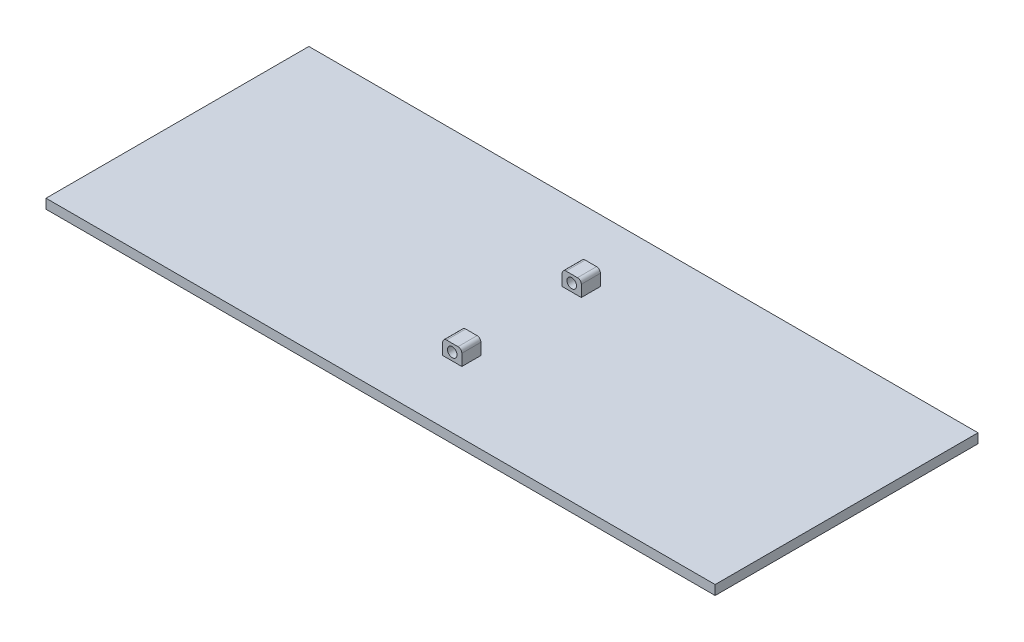
SolidWorks part; units mm, degrees
material "Alloy Steel"
ref_plane "Front Plane" through (0, 0, 0) normal (0, 0, 1) x (1, 0, 0)
ref_plane "Top Plane" through (0, 0, 0) normal (0, 1, 0) x (1, 0, 0)
ref_plane "Right Plane" through (0, 0, 0) normal (1, 0, 0) x (0, 0, -1)
sketch "Sketch1" plane through (0, 0, 0) normal (0, 1, 0) x (1, 0, 0)
  line L7 (0, 0) -> (3500, 0)
  line L8 (0, 0) -> (0, 1375)
  line L9 (0, 1375) -> (3500, 1375)
  line L10 (3500, 0) -> (3500, 1375)
  dimension "D1" = 1375
  dimension "D2" = 3500
extrude "Boss-Extrude1" add sketch "Sketch1" along normal blind 50
sketch "Sketch2" plane through (0, 50, 0) normal (0, 1, 0) x (1, 0, 0)
  line L1 (1750, 325) -> (1850, 325)
  line L2 (1750, 325) -> (1750, 425)
  line L3 (1750, 425) -> (1850, 425)
  line L4 (1850, 325) -> (1850, 425)
  line L5 (0, 0) -> (3500, 0) construction
  dimension "D1" = 1750
  dimension "D2" = 100
  dimension "D3" = 325
extrude "Boss-Extrude2" add sketch "Sketch2" along normal blind 80
fillet "Fillet1" radius 20 2 edges at (1850, 130, -375) (1750, 130, -375)
sketch "Sketch3" plane through (0, 0, 0) normal (0, 0, 1) x (1, 0, 0)
  line L2 (1800, 90) -> (1800, 130) construction
  line L3 (1770, 130) -> (1830, 130) construction
  circle A0 centre (1800, 90) radius 25
  dimension "D1" = 50
  dimension "D2" = 40
extrude "Cut-Extrude1" cut sketch "Sketch3" against normal through all
ref_plane "Plane1" through (0, 0, -687.5) normal (0, 0, -1) x (-1, 0, 0)
mirror "Mirror1" about plane through (0, 0, -687.5) normal (0, 0, -1) of "Cut-Extrude1", "Fillet1", "Boss-Extrude2"
sketch "Sketch5" plane through (0, 0, 0) normal (0, -1, 0) x (1, 0, 0)
  line L0 (0, 0) -> (3500, 0) construction
  line L1 (50, -50) -> (550, -50)
  line L2 (50, -50) -> (50, -637.5)
  line L3 (50, -637.5) -> (550, -637.5)
  line L4 (550, -50) -> (550, -637.5)
  line L5 (0, -1375) -> (0, 0) construction
  line L6 (2950, -50) -> (2950, -637.5)
  line L7 (630, -50) -> (630, -637.5)
  line L8 (630, -50) -> (1130, -50)
  line L9 (1130, -50) -> (1130, -637.5)
  line L10 (630, -637.5) -> (1130, -637.5)
  line L11 (1210, -50) -> (1210, -637.5)
  line L12 (1210, -50) -> (1710, -50)
  line L13 (1710, -50) -> (1710, -637.5)
  line L14 (1210, -637.5) -> (1710, -637.5)
  line L15 (1790, -50) -> (1790, -637.5)
  line L16 (1790, -50) -> (2290, -50)
  line L17 (2290, -50) -> (2290, -637.5)
  line L18 (1790, -637.5) -> (2290, -637.5)
  line L19 (2370, -50) -> (2370, -637.5)
  line L20 (2370, -50) -> (2870, -50)
  line L21 (2870, -50) -> (2870, -637.5)
  line L22 (2370, -637.5) -> (2870, -637.5)
  line L23 (630, -737.5) -> (630, -1325)
  line L24 (630, -737.5) -> (1130, -737.5)
  line L25 (1130, -737.5) -> (1130, -1325)
  line L26 (630, -1325) -> (1130, -1325)
  line L27 (1210, -737.5) -> (1210, -1325)
  line L28 (1210, -737.5) -> (1710, -737.5)
  line L29 (1710, -737.5) -> (1710, -1325)
  line L30 (1210, -1325) -> (1710, -1325)
  line L31 (1790, -737.5) -> (1790, -1325)
  line L32 (1790, -737.5) -> (2290, -737.5)
  line L33 (2290, -737.5) -> (2290, -1325)
  line L34 (1790, -1325) -> (2290, -1325)
  line L35 (2370, -737.5) -> (2370, -1325)
  line L36 (2370, -737.5) -> (2870, -737.5)
  line L37 (2870, -737.5) -> (2870, -1325)
  line L38 (2370, -1325) -> (2870, -1325)
  line L39 (50, -737.5) -> (50, -1325)
  line L40 (50, -737.5) -> (550, -737.5)
  line L41 (550, -737.5) -> (550, -1325)
  line L42 (50, -1325) -> (550, -1325)
  line L43 (3500, -1375) -> (0, -1375) construction
  line L44 (0, -1375) -> (0, 0) construction
  line L45 (2950, -50) -> (3450, -50)
  line L46 (3450, -50) -> (3450, -637.5)
  line L47 (2950, -637.5) -> (3450, -637.5)
  line L48 (2950, -737.5) -> (2950, -1325)
  line L49 (2950, -737.5) -> (3450, -737.5)
  line L50 (3450, -737.5) -> (3450, -1325)
  line L51 (2950, -1325) -> (3450, -1325)
  line L52 (3500, 0) -> (3500, -1375) construction
  point P10 (0, -687.5)
  dimension "D1" = 50
  dimension "D2" = 50
  dimension "D3" = 50
  dimension "D4" = 500
  dimension "D7" = 50
  dimension "D8" = 50
  dimension "D9" = 50
  dimension "D5" = 6
  dimension "D6" = 2
extrude "Boss-Extrude3" add sketch "Sketch5" along normal blind 20
sketch "Sketch7" plane through (0, -20, 0) normal (0, -1, 0) x (1, 0, 0)
  line L5 (50, -50) -> (50, -637.5) construction
  line L11 (150, -637.5215) -> (150, -49.9961)
  line L15 (162.369, -637.5215) -> (162.369, -49.9961)
  line L17 (150, -49.9961) -> (162.369, -49.9961)
  line L18 (150, -637.5215) -> (162.369, -637.5215)
  point P0 (218.8025, -637.3016)
  dimension "D1" = 100
  dimension "D4" = 12.369
extrude "Cut-Extrude3" cut sketch "Sketch7" against normal up to vertex (20 mm away) up to point (50, 0, -637.5)
pattern_linear "LPattern1" count 11 spacing 30 along (1, 0, 0) of "Cut-Extrude3"
sketch "Sketch9" plane through (0, -20, 0) normal (0, -1, 0) x (1, 0, 0)
  line L0 (50, -50) -> (50, -100)
  line L1 (150, -50) -> (50, -50) construction
  line L2 (50, -50) -> (100, -50)
  line L4 (50, -50) -> (50, -637.5) construction
  line L5 (50, -100) -> (100, -50)
  line L6 (550, -50) -> (500, -50)
  line L7 (550, -50) -> (550, -100)
  line L9 (500, -50) -> (550, -100)
  line L10 (50, -637.5) -> (50, -587.5)
  line L12 (50, -637.5) -> (100, -637.5)
  line L13 (50, -637.5) -> (150, -637.5) construction
  line L14 (550, -637.5) -> (550, -587.5)
  line L16 (550, -637.5) -> (500, -637.5)
  line L18 (50, -587.5) -> (100, -637.5)
  line L19 (500, -637.5) -> (550, -587.5)
  line L20 (50, -50) -> (50, -637.5) construction
  line L21 (462.369, -637.5) -> (550, -637.5) construction
  line L22 (550, -637.5) -> (550, -50) construction
  dimension "D1" = 50
  dimension "D2" = 50
  dimension "D3" = 50
  dimension "D4" = 50
  dimension "D5" = 50
  dimension "D6" = 50
  dimension "D7" = 50
  dimension "D8" = 50
  dimension "D9" = 500
  dimension "D10" = 0
  dimension "D11" = 0
  dimension "D12" = 0
  dimension "D13" = 0
  dimension "D14" = 0
  dimension "D15" = 0
extrude "Cut-Extrude4" cut sketch "Sketch9" against normal up to vertex (20 mm away) up to point (150, 0, -637.5)
pattern_linear "LPattern3" count 6 spacing 580 along (1, 0, 0) count 2 spacing 687.5 along (0, 0, -1) of "Cut-Extrude3", "LPattern1", "Cut-Extrude4"
sketch "Sketch10" plane through (0, -20, 0) normal (0, -1, 0) x (1, 0, 0)
  line L0 (50, -250) -> (3450, -250)
  line L3 (3450, -250) -> (3450, -270)
  line L4 (3450, -270) -> (50, -270)
  line L5 (50, -270) -> (50, -250)
  line L7 (50, -417.5) -> (3450, -417.5)
  line L8 (50, -417.5) -> (50, -437.5)
  line L9 (50, -437.5) -> (3450, -437.5)
  line L10 (3450, -417.5) -> (3450, -437.5)
  line L12 (50, -937.5) -> (3450, -937.5)
  line L13 (50, -937.5) -> (50, -957.5)
  line L14 (50, -957.5) -> (3450, -957.5)
  line L15 (3450, -937.5) -> (3450, -957.5)
  line L18 (50, -1105) -> (3450, -1105)
  line L19 (50, -1105) -> (50, -1125)
  line L20 (50, -1125) -> (3450, -1125)
  line L21 (3450, -1105) -> (3450, -1125)
  line L22 (50, -100) -> (50, -587.5) construction
  line L28 (50, -787.5) -> (50, -1275) construction
  line L29 (50, -787.5) -> (50, -1275) construction
  line L30 (150, -50) -> (100, -50) construction
  line L31 (100, -637.5) -> (150, -637.5) construction
  line L33 (50, -100) -> (50, -587.5) construction
  line L34 (150, -737.5) -> (100, -737.5) construction
  line L35 (100, -1325) -> (150, -1325) construction
  line L36 (3450, -587.5) -> (3450, -100) construction
  dimension "D1" = 20
  dimension "D2" = 20
  dimension "D3" = 0
  dimension "D4" = 0
  dimension "D5" = 20
  dimension "D6" = 20
  dimension "D7" = 0
  dimension "D8" = 0
  dimension "D9" = 200
  dimension "D10" = 200
  dimension "D11" = 200
  dimension "D12" = 200
  dimension "D13" = 0
extrude "Boss-Extrude4" add sketch "Sketch10" along normal blind 2
equation "\"l\"= 3.5"
equation "\"w\"= 1.375"
equation "\"A\"= \"l\" * \"w\""
equation "\"D2@Sketch1\"=\"l\""
equation "\"D1@Sketch1\"=\"w\""
